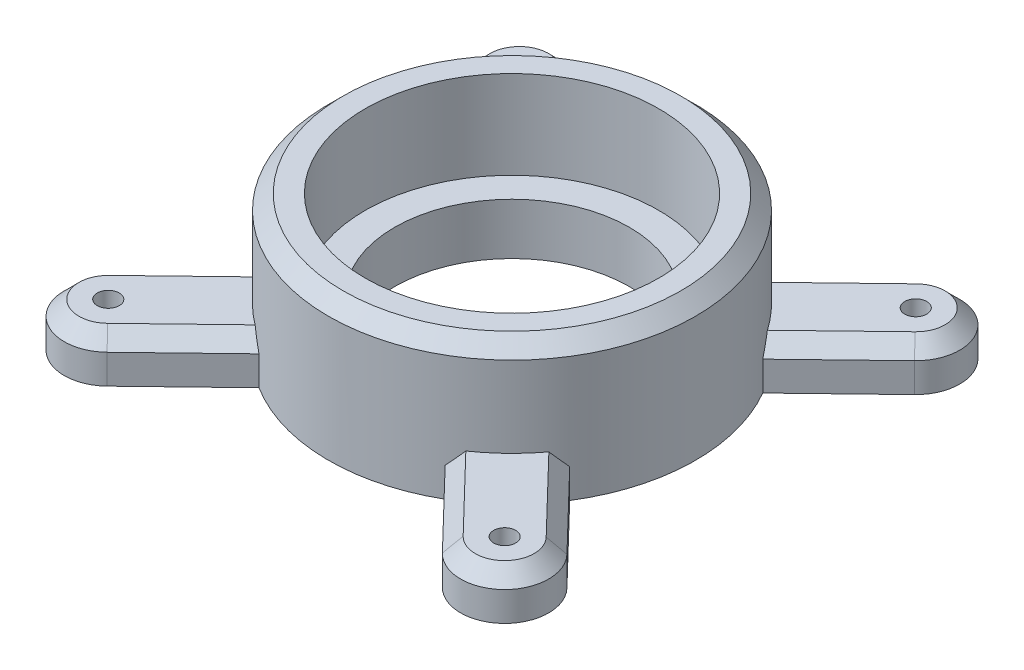
SolidWorks part; units mm, degrees
ref_plane "Front Plane" through (0, 0, 0) normal (0, 0, 1) x (1, 0, 0)
ref_plane "Top Plane" through (0, 0, 0) normal (0, 1, 0) x (1, 0, 0)
ref_plane "Right Plane" through (0, 0, 0) normal (1, 0, 0) x (0, 0, -1)
sketch "Sketch1" plane through (0, 0, 0) normal (0, 1, 0) x (1, 0, 0)
  line L0 (0, 0) -> (-27, 0) construction
  line L1 (-27, 0) -> (-27, 28) construction
  line L2 (0, 0) -> (0, 25) construction
  line L3 (0, 0) -> (-27, 28) construction
  line L6 (-12.5271, 21.6349) -> (-22.6809, 32.1648)
  line L7 (-21.1653, 13.3053) -> (-31.3191, 23.8352)
  line L8 (13.3053, 21.1653) -> (23.8352, 31.3191)
  line L9 (21.6349, 12.5271) -> (32.1648, 22.6809)
  line L10 (21.1653, -13.3053) -> (31.3191, -23.8352)
  line L11 (12.5271, -21.6349) -> (22.6809, -32.1648)
  line L12 (-13.3053, -21.1653) -> (-23.8352, -31.3191)
  line L13 (-21.6349, -12.5271) -> (-32.1648, -22.6809)
  arc A0 (-21.1653, 13.3053) -> (-21.6349, -12.5271) centre (0, 0) ccw
  arc A2 (-22.6809, 32.1648) -> (-31.3191, 23.8352) centre (-27, 28) ccw
  arc A3 (32.1648, 22.6809) -> (23.8352, 31.3191) centre (28, 27) ccw
  arc A4 (22.6809, -32.1648) -> (31.3191, -23.8352) centre (27, -28) ccw
  arc A5 (-32.1648, -22.6809) -> (-23.8352, -31.3191) centre (-28, -27) ccw
  arc A6 (-13.3053, -21.1653) -> (12.5271, -21.6349) centre (0, 0) ccw
  arc A7 (21.1653, -13.3053) -> (21.6349, 12.5271) centre (0, 0) ccw
  arc A8 (13.3053, 21.1653) -> (-12.5271, 21.6349) centre (0, 0) ccw
  point P1 (-31.3191, 23.8352)
  point P3 (-13.5, 14)
  point P7 (-21.6349, 13.3053)
  point P28 (0, 0)
  dimension "D1" = 50
  dimension "D4" = 6
  dimension "D2" = 27
  dimension "D3" = 28
  dimension "D6" = 14.628
  dimension "D7" = 12
  dimension "D5" = 4
extrude "Boss-Extrude1" add sketch "Sketch1" along normal blind 6
sketch "Sketch2" plane through (0, 6, 0) normal (0, 1, 0) x (1, 0, 0)
  circle A0 centre (0, 0) radius 25
  dimension "D1" = 50
extrude "Boss-Extrude2" add sketch "Sketch2" along normal blind 13
sketch "Sketch3" plane through (0, 19, 0) normal (0, 1, 0) x (1, 0, 0)
  circle A0 centre (0, 0) radius 20
  dimension "D1" = 40
extrude "Cut-Extrude1" cut sketch "Sketch3" against normal blind 12
sketch "Sketch4" plane through (0, 7, 0) normal (0, 1, 0) x (1, 0, 0)
  circle A0 centre (0, 0) radius 16
  dimension "D1" = 32
extrude "Cut-Extrude2" cut sketch "Sketch4" against normal blind 19
sketch "Sketch7" plane through (0, 0, 0) normal (0, -1, 0) x (-1, 0, 0)
  point P0 (27, 28)
  point P3 (-28, 27)
  point P6 (-27, -28)
  point P9 (28, -27)
hole_wizard "Ø3.0 (3) Diameter Hole1" positions "Sketch7" profile "Sketch8" hole size "Ø3.0" standard "ANSI Metric" end condition through all
sketch "Sketch8" plane through (-27, 0, -28) normal (1, 0, 0) x (0, 0, -1)
  line L0 (0, 0) -> (0, 19)
  line L1 (0, 19) -> (1.5, 19)
  line L2 (1.5, 19) -> (1.5, 0)
  line L5 (1.5, 0) -> (0, 0)
  line L11 (0, -6.35) -> (0, 107.95) construction
  dimension "Thru Hole Dia." = 3
  dimension "Thru Hole Depth" = 19
chamfer "Chamfer1" distance 2 angle 45 1 edges at (0, 19, 25)
chamfer "Chamfer2" distance 2 angle 45 12 edges at (26.8999, 6, -17.604) (32.3191, 6, -31.1648) (18.5703, 6, -26.2422) (26.2422, 6, 18.5703) (31.1648, 6, 32.3191) (17.604, 6, 26.8999) (-18.5703, 6, 26.2422) (-32.3191, 6, 31.1648) (-26.8999, 6, 17.604) (-17.604, 6, -26.8999) (-31.1648, 6, -32.3191) (-26.2422, 6, -18.5703)
